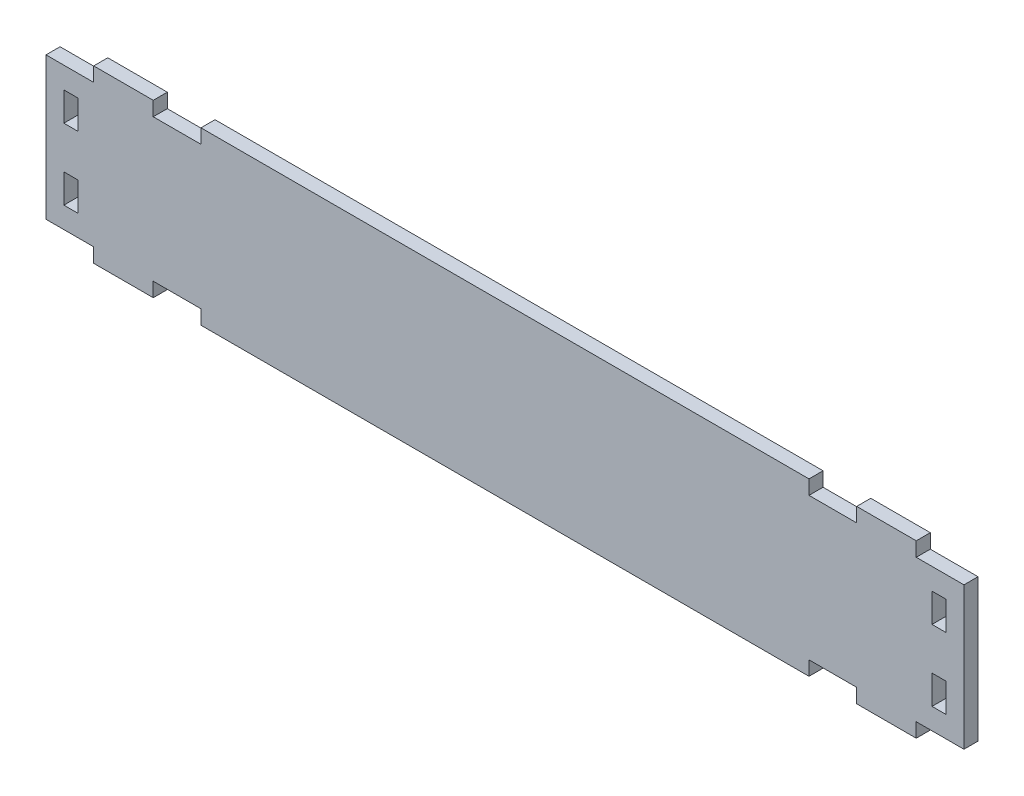
SolidWorks part; units mm, degrees
ref_plane "Front Plane" through (0, 0, 0) normal (0, 0, 1) x (1, 0, 0)
ref_plane "Top Plane" through (0, 0, 0) normal (0, 1, 0) x (1, 0, 0)
ref_plane "Right Plane" through (0, 0, 0) normal (1, 0, 0) x (0, 0, -1)
sketch "Sketch1" plane through (0, 0, 0) normal (0, 0, 1) x (1, 0, 0)
  line L0 (0, -5) -> (0, 55.8)
  line L1 (0, -5) -> (-326.39, -5)
  line L2 (0, 55.8) -> (-326.39, 55.8)
  line L3 (-326.39, -5) -> (-326.39, 55.8)
  dimension "D1" = 326.39
extrude "Boss-Extrude1" add sketch "Sketch1" along normal blind 5 contours L1 L3 L2 L0
sketch "Sketch2" plane through (0, 0, 5) normal (0, 0, 1) x (1, 0, 0)
  line L0 (-262.89, -5) -> (-262.89, 21.336)
  line L2 (0, 55.8) -> (-326.39, 55.8) construction
  line L4 (0, -5) -> (-326.39, -5) construction
  line L8 (-259.0556, 51.736) -> (-259.0556, -0.936)
  line L9 (-262.89, 55.8) -> (-262.89, 29.464)
  line L10 (-254.762, -5) -> (-254.762, 21.336)
  line L11 (-254.762, 55.8) -> (-254.762, 29.464)
  line L12 (-250.9276, 51.736) -> (-250.9276, -0.936)
  line L13 (-246.634, -5) -> (-246.634, 21.336)
  line L14 (-246.634, 55.8) -> (-246.634, 29.464)
  line L15 (-242.7996, 51.736) -> (-242.7996, -0.936)
  line L16 (-238.506, -5) -> (-238.506, 21.336)
  line L17 (-238.506, 55.8) -> (-238.506, 29.464)
  line L18 (-234.6716, 51.736) -> (-234.6716, -0.936)
  line L19 (-230.378, -5) -> (-230.378, 21.336)
  line L20 (-230.378, 55.8) -> (-230.378, 29.464)
  line L21 (-226.5436, 51.736) -> (-226.5436, -0.936)
  line L22 (-222.25, -5) -> (-222.25, 21.336)
  line L23 (-222.25, 55.8) -> (-222.25, 29.464)
  line L24 (-218.4156, 51.736) -> (-218.4156, -0.936)
  line L25 (-214.122, -5) -> (-214.122, 21.336)
  line L26 (-214.122, 55.8) -> (-214.122, 29.464)
  line L27 (-210.2876, 51.736) -> (-210.2876, -0.936)
  line L28 (-205.994, -5) -> (-205.994, 21.336)
  line L29 (-205.994, 55.8) -> (-205.994, 29.464)
  line L30 (-202.1596, 51.736) -> (-202.1596, -0.936)
  line L31 (-197.866, -5) -> (-197.866, 21.336)
  line L32 (-197.866, 55.8) -> (-197.866, 29.464)
  line L33 (-194.0316, 51.736) -> (-194.0316, -0.936)
  line L34 (-189.738, -5) -> (-189.738, 21.336)
  line L35 (-189.738, 55.8) -> (-189.738, 29.464)
  line L36 (-185.9036, 51.736) -> (-185.9036, -0.936)
  line L37 (-181.61, -5) -> (-181.61, 21.336)
  line L38 (-181.61, 55.8) -> (-181.61, 29.464)
  line L39 (-177.7756, 51.736) -> (-177.7756, -0.936)
  line L40 (-173.482, -5) -> (-173.482, 21.336)
  line L41 (-173.482, 55.8) -> (-173.482, 29.464)
  line L42 (-169.6476, 51.736) -> (-169.6476, -0.936)
  line L43 (-165.354, -5) -> (-165.354, 21.336)
  line L44 (-165.354, 55.8) -> (-165.354, 29.464)
  line L45 (-161.5196, 51.736) -> (-161.5196, -0.936)
  line L46 (-157.226, -5) -> (-157.226, 21.336)
  line L47 (-157.226, 55.8) -> (-157.226, 29.464)
  line L48 (-153.3916, 51.736) -> (-153.3916, -0.936)
  line L49 (-149.098, -5) -> (-149.098, 21.336)
  line L50 (-149.098, 55.8) -> (-149.098, 29.464)
  line L51 (-145.2636, 51.736) -> (-145.2636, -0.936)
  line L52 (-140.97, -5) -> (-140.97, 21.336)
  line L53 (-140.97, 55.8) -> (-140.97, 29.464)
  line L54 (-137.1356, 51.736) -> (-137.1356, -0.936)
  line L55 (-132.842, -5) -> (-132.842, 21.336)
  line L56 (-132.842, 55.8) -> (-132.842, 29.464)
  line L57 (-129.0076, 51.736) -> (-129.0076, -0.936)
  line L58 (-124.714, -5) -> (-124.714, 21.336)
  line L59 (-124.714, 55.8) -> (-124.714, 29.464)
  line L60 (-120.8796, 51.736) -> (-120.8796, -0.936)
  line L61 (-116.586, -5) -> (-116.586, 21.336)
  line L62 (-116.586, 55.8) -> (-116.586, 29.464)
  line L63 (-112.7516, 51.736) -> (-112.7516, -0.936)
  line L64 (-108.458, -5) -> (-108.458, 21.336)
  line L65 (-108.458, 55.8) -> (-108.458, 29.464)
  line L66 (-104.6236, 51.736) -> (-104.6236, -0.936)
  line L67 (-100.33, -5) -> (-100.33, 21.336)
  line L68 (-100.33, 55.8) -> (-100.33, 29.464)
  line L69 (-96.4956, 51.736) -> (-96.4956, -0.936)
  line L70 (-92.202, -5) -> (-92.202, 21.336)
  line L71 (-92.202, 55.8) -> (-92.202, 29.464)
  line L72 (-88.3676, 51.736) -> (-88.3676, -0.936)
  line L73 (-84.074, -5) -> (-84.074, 21.336)
  line L74 (-84.074, 55.8) -> (-84.074, 29.464)
  line L75 (-80.2396, 51.736) -> (-80.2396, -0.936)
  line L76 (-75.946, -5) -> (-75.946, 21.336)
  line L77 (-75.946, 55.8) -> (-75.946, 29.464)
  line L78 (-72.1116, 51.736) -> (-72.1116, -0.936)
  line L79 (-67.818, -5) -> (-67.818, 21.336)
  line L80 (-67.818, 55.8) -> (-67.818, 29.464)
  line L81 (-63.9836, 51.736) -> (-63.9836, -0.936)
  line L85 (-59.69, -5) -> (-59.69, 21.336) [skipped]
  line L86 (-59.69, 55.8) -> (-59.69, 29.464) [skipped]
  line L87 (-55.8556, 51.736) -> (-55.8556, -0.936) [skipped]
  dimension "D3" = 3.8344
  dimension "D5" = 4.064
  dimension "D6" = 26
surface "Surface-Extrude2" [suppressed] sketch "Sketch2" parameters "D1"=13.636
flatten bends "Flatten-Bends1" thickness 5 parameters "D1"=0
sketch "Sharp-Sketch1" plane through (0, 0, 0) normal (0, 0, -1) x (-1, 0, 0)
process bends "Process-Bends1" thickness 5 parameters "D1"=0
sketch "Flat-Sketch1" plane through (0, 0, 0) normal (0, 0, -1) x (-1, 0, 0)
sketch "Sketch9" plane through (0, 0, 5) normal (0, 0, 1) x (1, 0, 0)
  line L0 (-38.1346, -5) -> (-55.0939, -5) construction
  line L1 (-55.0939, -5) -> (-55.0939, 0.08) construction
  line L2 (-55.0939, 0.08) -> (-38.1346, 0.08) construction
  line L3 (-38.1346, 0.08) -> (-38.1346, -5) construction
  line L4 (0, -5) -> (-16.9592, -5) construction
  line L5 (-16.9592, -5) -> (-16.9592, 0.08) construction
  line L6 (-16.9592, 0.08) -> (0, 0.08) construction
  line L7 (0, 0.08) -> (0, -5) construction
  line L8 (-38.1346, -5) -> (-55.0939, -5)
  line L9 (-55.0939, -5) -> (-55.0939, 0.08)
  line L10 (-55.0939, 0.08) -> (-38.1346, 0.08)
  line L11 (-38.1346, 0.08) -> (-38.1346, -5)
  line L12 (0, -5) -> (-16.9592, -5)
  line L13 (-16.9592, -5) -> (-16.9592, 0.08)
  line L14 (-16.9592, 0.08) -> (0, 0.08)
  line L15 (0, 0.08) -> (0, -5)
  line L16 (-16.9592, 55.8) -> (0, 55.8) construction
  line L17 (0, 55.8) -> (0, 50.72) construction
  line L18 (0, 50.72) -> (-16.9592, 50.72) construction
  line L19 (-16.9592, 50.72) -> (-16.9592, 55.8) construction
  line L20 (-55.0939, 55.8) -> (-38.1346, 55.8) construction
  line L21 (-38.1346, 55.8) -> (-38.1346, 50.72) construction
  line L22 (-38.1346, 50.72) -> (-55.0939, 50.72) construction
  line L23 (-55.0939, 50.72) -> (-55.0939, 55.8) construction
  line L24 (-16.9592, 55.8) -> (0, 55.8)
  line L25 (0, 55.8) -> (0, 50.72)
  line L26 (0, 50.72) -> (-16.9592, 50.72)
  line L27 (-16.9592, 50.72) -> (-16.9592, 55.8)
  line L28 (-55.0939, 55.8) -> (-38.1346, 55.8)
  line L29 (-38.1346, 55.8) -> (-38.1346, 50.72)
  line L30 (-38.1346, 50.72) -> (-55.0939, 50.72)
  line L31 (-55.0939, 50.72) -> (-55.0939, 55.8)
  line L32 (-163.195, -5) -> (-163.195, 55.8) construction
  line L33 (-163.195, -5) -> (-163.195, 55.8) construction
  line L34 (-271.2961, 50.72) -> (-271.2961, 55.8)
  line L35 (-288.2554, 50.72) -> (-271.2961, 50.72)
  line L36 (-288.2554, 55.8) -> (-288.2554, 50.72)
  line L37 (-271.2961, 55.8) -> (-288.2554, 55.8)
  line L38 (-309.4308, 50.72) -> (-309.4308, 55.8)
  line L39 (-326.39, 50.72) -> (-309.4308, 50.72)
  line L40 (-326.39, 55.8) -> (-326.39, 50.72)
  line L41 (-309.4308, 55.8) -> (-326.39, 55.8)
  line L42 (-326.39, 0.08) -> (-326.39, -5)
  line L43 (-309.4308, 0.08) -> (-326.39, 0.08)
  line L44 (-309.4308, -5) -> (-309.4308, 0.08)
  line L45 (-326.39, -5) -> (-309.4308, -5)
  line L46 (-288.2554, 0.08) -> (-288.2554, -5)
  line L47 (-271.2961, 0.08) -> (-288.2554, 0.08)
  line L48 (-271.2961, -5) -> (-271.2961, 0.08)
  line L49 (-288.2554, -5) -> (-271.2961, -5)
extrude "Cut-Extrude2" cut sketch "Sketch9" against normal blind 5.08 normal cut yes
sketch "Sketch11" plane through (0, 0, 0) normal (0, 0, -1) x (-1, 0, 0)
  line L0 (163.195, -5) -> (163.195, 55.8) construction
  line L1 (11.35, 43.1043) -> (6.35, 43.1043)
  line L2 (11.35, 43.1043) -> (11.35, 32.8495)
  line L3 (11.35, 32.8495) -> (6.35, 32.8495)
  line L4 (6.35, 43.1043) -> (6.35, 32.8495)
  line L5 (11.35, 17.8705) -> (6.35, 17.8705)
  line L6 (11.35, 17.8705) -> (11.35, 7.6157)
  line L7 (11.35, 7.6157) -> (6.35, 7.6157)
  line L8 (6.35, 17.8705) -> (6.35, 7.6157)
  line L9 (163.195, -5) -> (163.195, 55.8) construction
  line L10 (320.04, 17.8705) -> (320.04, 7.6157)
  line L11 (315.04, 7.6157) -> (320.04, 7.6157)
  line L12 (315.04, 17.8705) -> (315.04, 7.6157)
  line L13 (315.04, 17.8705) -> (320.04, 17.8705)
  line L14 (320.04, 43.1043) -> (320.04, 32.8495)
  line L15 (315.04, 32.8495) -> (320.04, 32.8495)
  line L16 (315.04, 43.1043) -> (315.04, 32.8495)
  line L17 (315.04, 43.1043) -> (320.04, 43.1043)
extrude "Cut-Extrude3" cut sketch "Sketch11" against normal up to next normal cut yes
sketch "Bend-Lines1" plane through (0, 0, 0) normal (0, 1, 0) x (1, 0, 0)
sketch "Bounding-Box1" plane through (0, 0, 0) normal (0, 1, 0) x (1, 0, 0)
sheet metal parameters "Sheet-Metal78" thickness 5 parameters "D1"=63.5
flat pattern "Flat-Pattern78" [suppressed]
sketch "Bend-Lines2" plane through (0, 0, 0) normal (0, 1, 0) x (1, 0, 0)
sketch "Bounding-Box2" [suppressed] plane through (0, 0, 0) normal (0, 1, 0) x (1, 0, 0)
sheet metal parameters "Sheet-Metal79" thickness 5 parameters "D1"=63.5
flat pattern "Flat-Pattern78"
sketch "Bend-Lines2" plane through (0, 0, 0) normal (0, 1, 0) x (1, 0, 0)
sketch "Bounding-Box2" [suppressed] plane through (0, 0, 0) normal (0, 1, 0) x (1, 0, 0)
sheet metal parameters "Sheet-Metal80" thickness 5 parameters "D1"=63.5
flat pattern "Flat-Pattern78"
sketch "Bend-Lines2" plane through (0, 0, 0) normal (0, 1, 0) x (1, 0, 0)
sketch "Bounding-Box2" [suppressed] plane through (0, 0, 0) normal (0, 1, 0) x (1, 0, 0)
equation "\"thicknes\"=0.19685"
